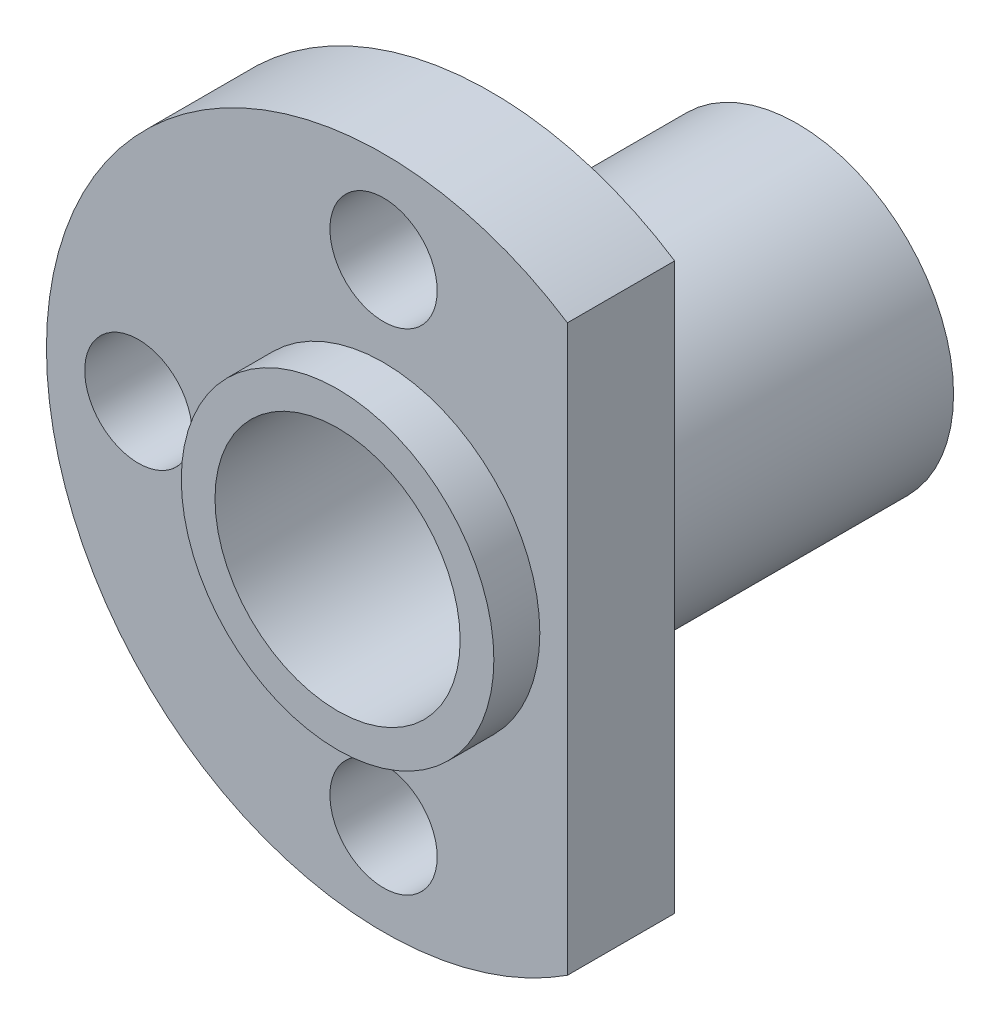
SolidWorks part; units mm, degrees
material "Brass"
ref_plane "Front Plane" through (0, 0, 0) normal (0, 0, 1) x (1, 0, 0)
ref_plane "Top Plane" through (0, 0, 0) normal (0, 1, 0) x (1, 0, 0)
ref_plane "Right Plane" through (0, 0, 0) normal (1, 0, 0) x (0, 0, -1)
sketch "Sketch1" plane through (0, 0, 0) normal (0, 0, 1) x (1, 0, 0)
  circle A0 centre (0, 0) radius 11
  circle A1 centre (0, 0) radius 5.1
  circle A2 centre (0, 0) radius 8 construction
  circle A3 centre (0, 8) radius 1.75
  circle A4 centre (8, 0) radius 1.75
  circle A5 centre (0, -8) radius 1.75
  circle A6 centre (-8, 0) radius 1.75
  point P16 (0, 0)
  dimension "D1" = 22
  dimension "D2" = 10.2
  dimension "D3" = 16
  dimension "D4" = 3.5
  dimension "D5" = 4
extrude "Boss-Extrude1" add sketch "Sketch1" against normal blind 3.5
sketch "Sketch2" plane through (0, 0, 0) normal (0, 0, 1) x (1, 0, 0)
  circle A0 centre (0, 0) radius 5.1
  circle A1 centre (0, 0) radius 4
  dimension "D1" = 8
extrude "Boss-Extrude2" add sketch "Sketch2" along normal blind 1.5 and the other way blind 13.5
sketch "Sketch3" plane through (0, 0, 1.5) normal (0, 0, 1) x (1, 0, 0)
  circle A0 centre (0, 0) radius 4
curve "Helix/Spiral1" pitch 2 height 15 turns 7.5
sketch "Sketch4" plane through (0, 0, 0) normal (0, 1, 0) x (1, 0, 0)
  line L0 (3, -0.55) -> (3, -2.45)
  line L1 (3, -2.45) -> (5, -1.7146)
  line L2 (5, -1.7146) -> (5, -1.2854)
  line L3 (5, -1.2854) -> (3, -0.55)
  line L4 (3, -1.5) -> (5, -1.5)
  point P6 (4, -1.5)
  dimension "D1" = 1.9
  dimension "D2" = 2
  dimension "D3" = 69.811
sweep "Cut-Sweep1" [suppressed] cut profiles "Sketch4" path "Helix/Spiral1"
fillet "Fillet2" [suppressed] radius 0.3
sketch "Croquis1" plane through (0, 0, 0) normal (0, 0, 1) x (1, 0, 0)
  line L1 (6, 12.3843) -> (19.1379, 12.3843)
  line L2 (6, 12.3843) -> (6, -11.484)
  line L3 (6, -11.484) -> (19.1379, -11.484)
  line L4 (19.1379, 12.3843) -> (19.1379, -11.484)
  dimension "D1" = 6
extrude "Cortar-Extruir1" cut sketch "Croquis1" against normal through all
